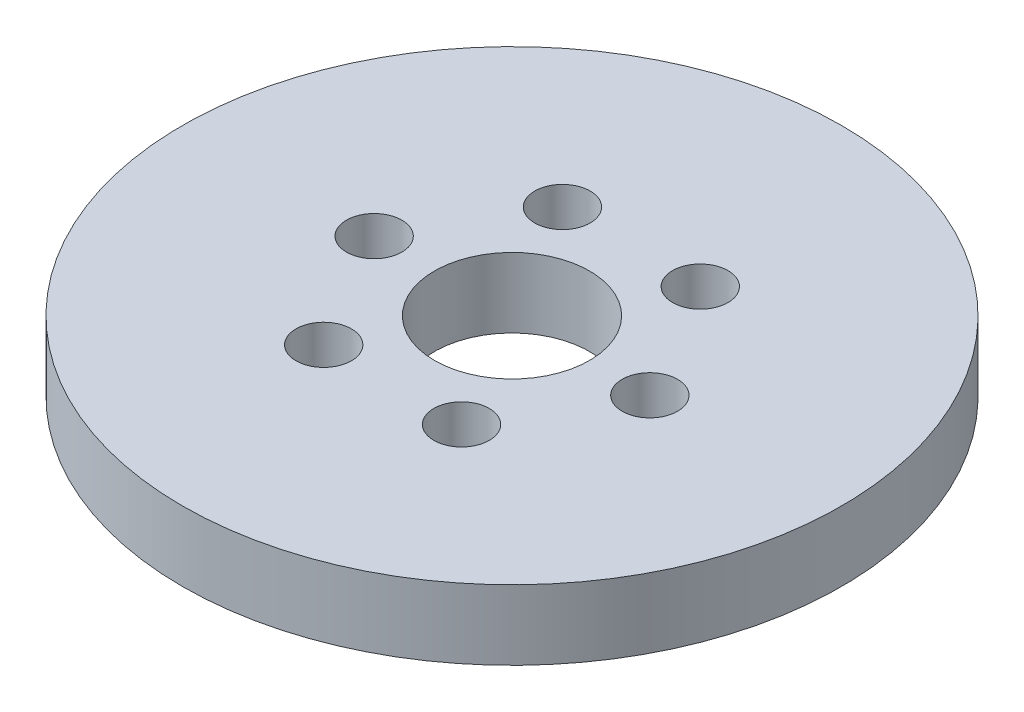
SolidWorks part; units mm, degrees
ref_plane "Front Plane" through (0, 0, 0) normal (0, 0, 1) x (1, 0, 0)
ref_plane "Top Plane" through (0, 0, 0) normal (0, 1, 0) x (1, 0, 0)
ref_plane "Right Plane" through (0, 0, 0) normal (1, 0, 0) x (0, 0, -1)
sketch "Sketch1" plane through (0, 0, 0) normal (0, 1, 0) x (1, 0, 0)
  circle A0 centre (0, 0) radius 85
  dimension "FLANGE_OD" = 170
extrude "Boss-Extrude1" add sketch "Sketch1" along normal blind 18
sketch "Sketch2" plane through (0, 0, 0) normal (0, 1, 0) x (1, 0, 0)
  circle A0 centre (0, 0) radius 20
  dimension "BORE_D" = 40
extrude "Cut-Extrude1" cut sketch "Sketch2" along normal through all
sketch "Sketch3" plane through (0, 18, 0) normal (0, 1, 0) x (1, 0, 0)
  circle A0 centre (0, 0) radius 35.5514 construction
  circle A1 centre (-35.5514, 0) radius 7.148
  dimension "BOLT_D" = 14.296
  dimension "BOLT_PCD" = 71.1027
extrude "Cut-Extrude2" cut sketch "Sketch3" against normal blind 14.3152
pattern_circular "CirPattern1" count 6 over 360 about axis through (0, 0, 0) along (0, 1, 0) of "Cut-Extrude2"
